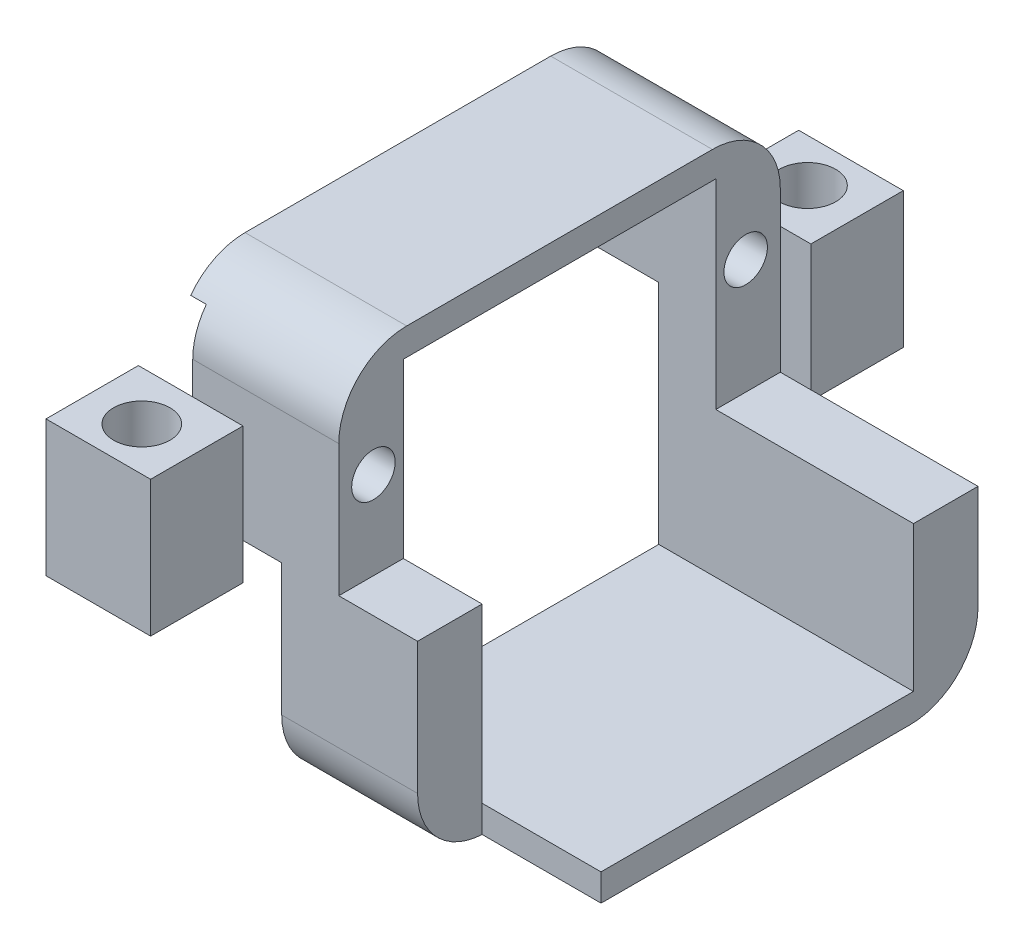
SolidWorks part; units mm, degrees
ref_plane "Front Plane" through (0, 0, 0) normal (0, 0, 1) x (1, 0, 0)
ref_plane "Top Plane" through (0, 0, 0) normal (0, 1, 0) x (1, 0, 0)
ref_plane "Right Plane" through (0, 0, 0) normal (1, 0, 0) x (0, 0, -1)
sketch "Sketch1" plane through (0, 0, 0) normal (0, 1, 0) x (1, 0, 0)
  line L0 (-1.1, 16.25) -> (-1.1, 11.5)
  line L1 (-17.65, -16.25) -> (17.65, -16.25)
  line L2 (-17.65, -16.25) -> (-17.65, 16.25)
  line L3 (-17.65, 16.25) -> (17.65, 16.25)
  line L4 (17.65, -16.25) -> (17.65, 16.25)
  line L5 (-17.65, -16.25) -> (17.65, 16.25) construction
  line L6 (-17.65, 16.25) -> (17.65, -16.25) construction
  line L7 (-1.1, 11.5) -> (17.65, 11.5)
  line L8 (-1.1, -16.25) -> (-1.1, -11.5)
  line L9 (-1.1, -11.5) -> (17.65, -11.5)
  line L10 (-1.1, 11.5) -> (-1.1, -11.5) construction
  line L11 (8.9, -11.5) -> (8.9, -16.25)
  line L12 (-8.8, 16.25) -> (-8.8, 11.5)
  line L13 (-8.8, 11.5) -> (-3.8, 11.5)
  line L14 (-3.8, 11.5) -> (-3.8, 16.25)
  line L15 (-3.8, -16.25) -> (-3.8, -11.5)
  line L16 (-3.8, -11.5) -> (-8.8, -11.5)
  line L17 (-8.8, -11.5) -> (-8.8, -16.25)
  line L18 (-8.8, 11.5) -> (-8.8, -11.5)
  line L19 (5.35, 16.25) -> (5.35, 23.05)
  line L20 (5.35, 23.05) -> (-2.35, 23.05)
  line L21 (-2.35, 23.05) -> (-2.35, 16.25)
  line L22 (-11.65, -16.25) -> (-11.65, -23.05)
  line L23 (-11.65, -23.05) -> (-3.95, -23.05)
  line L24 (-3.95, -23.05) -> (-3.95, -16.25)
  line L25 (9.53, -16.25) -> (9.53, -23.05)
  line L26 (9.53, -23.05) -> (17.23, -23.05)
  line L27 (17.23, -23.05) -> (17.23, -16.25)
  line L28 (-1.1, 11.5) -> (-1.1, -11.5)
  circle A0 centre (1.5, 19.85) radius 2.075
  circle A1 centre (13.38, -19.85) radius 2.075
  circle A2 centre (-7.8, -19.85) radius 2.075
  point P0 (0, 0)
  point P11 (-1.1, 0)
  point P31 (1.5, 23.05)
  point P45 (-7.8, -23.05)
  point P48 (13.38, -23.05)
  dimension "D11" = 4.15
  dimension "D18" = 4.15
  dimension "D19" = 4.15
  dimension "D1" = 32.5
  dimension "D2" = 23
  dimension "D3" = 8.75
  dimension "D4" = 10
  dimension "D5" = 16.55
  dimension "D6" = 2.7
  dimension "D7" = 5
  dimension "D8" = 1.5
  dimension "D9" = 7.7
  dimension "D10" = 6.8
  dimension "D12" = 9.85
  dimension "D13" = 31.03
  dimension "D14" = 7.7
  dimension "D15" = 19.85
  dimension "D16" = 7.7
  dimension "D17" = 6.8
  dimension "D20" = 19.85
extrude "Boss-Extrude1" add sketch "Sketch1" against normal blind 2 contours L7 L28 L9 L4 | L0 L7 L4 L3 | L11 L9 L8 L1 region at (8.275, 0, -13.875) region at (8.275, 0, 0) region at (3.9, 0, 13.875)
extrude "Boss-Extrude2" add sketch "Sketch1<3>" along normal blind 12.7 contours L0 L7 L4 L3 | L11 L9 L8 L1 region at (8.275, 0, -13.875) region at (3.9, 0, 13.875)
sketch "Sketch1<3>" plane through (0, 0, 0) normal (0, 1, 0) x (1, 0, 0) same geometry as "Sketch1"
sketch "Sketch3" plane through (0, 0, 0) normal (0, 1, 0) x (1, 0, 0)
  line L0 (3.1, 16.25) -> (3.1, 11.5)
  line L1 (-17.65, 16.25) -> (17.65, 16.25) construction
  line L2 (-1.1, 11.5) -> (17.65, 11.5) construction
  line L3 (3.1, 11.5) -> (-17.65, 11.5)
  line L4 (-17.65, -16.25) -> (-17.65, 16.25) construction
  line L5 (3.1, -16.25) -> (3.1, -11.5)
  line L6 (-17.65, -16.25) -> (17.65, -16.25) construction
  line L7 (-1.1, -11.5) -> (17.65, -11.5) construction
  line L8 (3.1, -11.5) -> (-17.65, -11.5)
  line L9 (3.1, 11.5) -> (3.1, -11.5)
  line L10 (-7.65, -11.5) -> (-7.65, -16.275)
  line L11 (3.1, 16.25) -> (-17.65, 16.25)
  line L12 (-17.65, 16.25) -> (-17.65, 11.5)
  line L13 (-17.65, -11.5) -> (-17.65, -16.25)
  line L14 (-17.65, -16.25) -> (3.1, -16.25)
  line L15 (-8.8, 11.5) -> (-8.8, -11.5)
  line L16 (-8.8, 11.5) -> (-8.8, 16.25)
  line L17 (-8.8, -11.5) -> (-8.8, -16.25)
  dimension "D1" = 20.75
  dimension "D2" = 10
extrude "Boss-Extrude3" add sketch "Sketch3" along normal blind 12.7 from surface contours L11 L12 L3 L0 | L10 L14 L5 L8 region at (-2.85, 0, -13.875) region at (-2.275, 0, 13.875) starting at face at (8.275, 12.7, -13.875)
extrude "Boss-Extrude4" add sketch "Sketch3<3>" along normal blind 2 from surface contours L16 L3 L0 L11 | L3 L15 L8 L9 | L10 L14 L5 L8 | L8 L17 L14 L10 region at (-2.85, 0, -13.875) region at (-2.85, 0, 0) region at (-2.275, 0, 13.875) region at (-8.225, 0, 13.875) starting at face at (-2.275, 25.4, 13.875)
sketch "Sketch3<3>" plane through (0, 0, 0) normal (0, 1, 0) x (1, 0, 0) same geometry as "Sketch3"
sketch "Sketch2" plane through (0, 0, 0) normal (1, 0, 0) x (0, 0, -1)
  line L0 (13.7, 6.45) -> (-13.7, 6.45) construction
  line L1 (-13.7, 19.15) -> (13.7, 19.15) construction
  circle A0 centre (13.7, 6.45) radius 1.6
  circle A1 centre (-13.7, 6.45) radius 1.6
  circle A2 centre (-13.7, 19.15) radius 1.6
  circle A3 centre (13.7, 19.15) radius 1.6
  point P4 (0, 6.45)
  dimension "D1" = 3.2
  dimension "D2" = 3.2
  dimension "D6" = 3.2
  dimension "D7" = 3.2
  dimension "D3" = 27.4
  dimension "D4" = 6.45
  dimension "D5" = 6.45
extrude "Cut-Extrude1" cut sketch "Sketch2" along normal blind 8 from surface contours A1 | A0 region at (0, 6.45, -13.7) region at (0, 6.45, 13.7) starting at face at (-1.1, 5.85, 0)
extrude "Cut-Extrude2" cut sketch "Sketch2<3>" against normal blind 8 from surface contours A3 | A2 region at (0, 19.15, 13.7) region at (0, 19.15, -13.7) starting at face at (3.1, 19.55, 0)
sketch "Sketch2<3>" plane through (0, 0, 0) normal (1, 0, 0) x (0, 0, -1) same geometry as "Sketch2"
extrude "Boss-Extrude5" add sketch "Sketch1<4>" along normal blind 10 from offset 10 contours L20 L21 L3 L19 A0 | L23 L24 L1 L22 A2 region at (-1.725, 0, -16.3527) region at (-4.0527, 0, 19.65)
sketch "Sketch1<4>" plane through (0, 0, 0) normal (0, 1, 0) x (1, 0, 0) same geometry as "Sketch1"
fillet "Fillet1" radius 5 4 edges at (3.9, -2, 16.25) (-2.85, 27.4, 16.25) (8.275, -2, -16.25) (-2.85, 27.4, -16.25)
sketch "Sketch5" plane through (0, 0, 0) normal (0, 1, 0) x (1, 0, 0)
  line L1 (17.65, 16.25) -> (3.1, 16.25)
  line L2 (17.65, 16.25) -> (17.65, 11.5)
  line L3 (17.65, 11.5) -> (3.1, 11.5)
  line L4 (3.1, 16.25) -> (3.1, 11.5)
extrude "Cut-Extrude3" cut sketch "Sketch5" against normal blind 2 from surface starting at face at (9.37, 12.7, -14.35)
sketch "Sketch6" plane through (0, 0, 0) normal (0, 1, 0) x (1, 0, 0)
  line L1 (-8.8, 11.5) -> (-1.1, 11.5)
  line L2 (-8.8, 11.5) -> (-8.8, 16.25)
  line L3 (-8.8, 16.25) -> (-1.1, 16.25)
  line L4 (-1.1, 11.5) -> (-1.1, 16.25)
extrude "Cut-Extrude4" cut sketch "Sketch6" along normal blind 4 from surface starting at face at (-4.43, 12.7, -14.35)
